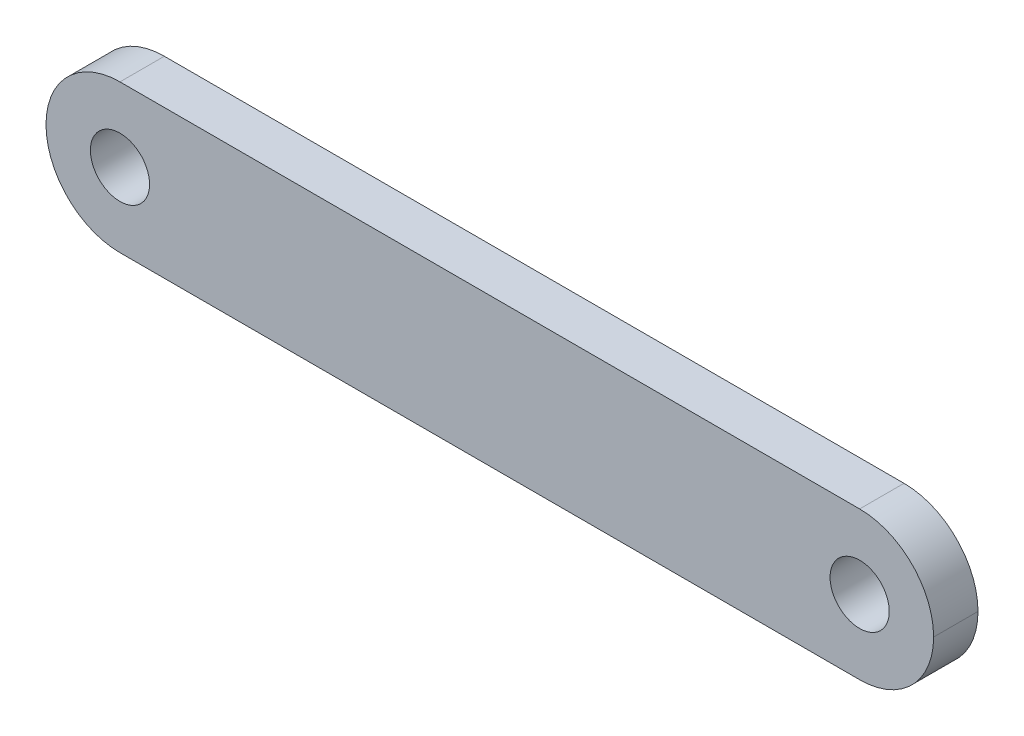
SolidWorks part; units mm, degrees
ref_plane "Front" through (0, 0, 0) normal (0, 0, 1) x (1, 0, 0)
ref_plane "Top" through (0, 0, 0) normal (0, 1, 0) x (1, 0, 0)
ref_plane "Right" through (0, 0, 0) normal (1, 0, 0) x (0, 0, -1)
sketch "Esquisse1" plane through (0, 0, 0) normal (0, 0, 1) x (1, 0, 0)
  line L0 (0, 10) -> (10, 10) construction
  line L1 (0, 0) -> (120, 0)
  line L2 (0, 0) -> (0, 20)
  line L3 (0, 20) -> (120, 20)
  line L4 (120, 0) -> (120, 20)
  line L5 (60, 0) -> (60, 20) construction
  circle A0 centre (10, 10) radius 4
  circle A1 centre (110, 10) radius 4
  dimension "D2" = 8
  dimension "D4" = 100
  dimension "D1" = 20
  dimension "D3" = 10
extrude "Boss.-Extru.1" add sketch "Esquisse1" along normal blind 6
fillet "Congé1" radius 10 4 edges at (120, 20, 3) (120, 0, 3) (0, 0, 3) (0, 20, 3)
